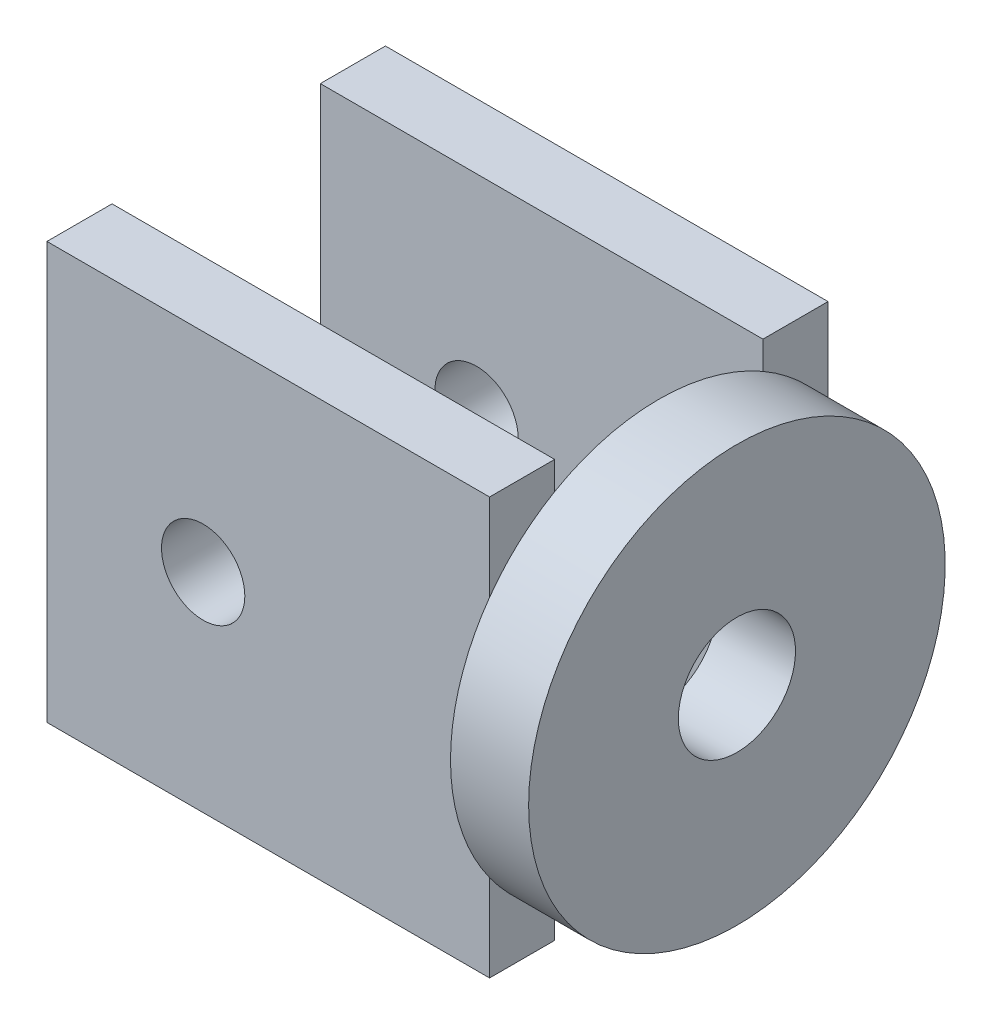
SolidWorks part; units mm, degrees
ref_plane "Front Plane" through (0, 0, 0) normal (0, 0, 1) x (1, 0, 0)
ref_plane "Top Plane" through (0, 0, 0) normal (0, 1, 0) x (1, 0, 0)
ref_plane "Right Plane" through (0, 0, 0) normal (1, 0, 0) x (0, 0, -1)
sketch "Base Sketch" plane through (0, 0, 0) normal (0, 0, 1) x (1, 0, 0)
  line L0 (-3000, 0) -> (3000, 0) construction
  line L1 (-3, 0) -> (0, 0)
  line L2 (0, 0) -> (0, 8)
  line L3 (0, 8) -> (-3, 8)
  line L4 (-3, 8) -> (-3, 0)
revolve "Base" add sketch "Base Sketch" angle 360 about L0
ref_axis "Engine Axis" through (1, 0, 0) along (-1, 0, 0)
sketch "Cheek Block Sketch" plane through (0, 0, 0) normal (0, 0, 1) x (1, 0, 0)
  line L0 (-20, -8) -> (-3, -8)
  line L1 (-3, -8) -> (-3, 8)
  line L2 (-3, 8) -> (-20, 8)
  line L3 (-20, 8) -> (-20, -8)
extrude "Cheek Block" add sketch "Cheek Block Sketch" along normal mid plane 13
sketch "Gap Sketch" plane through (0, 0, 0) normal (0, 0, 1) x (1, 0, 0)
  line L0 (-21, -9) -> (-3, -9)
  line L1 (-3, -9) -> (-3, 9)
  line L2 (-3, 9) -> (-21, 9)
  line L3 (-21, 9) -> (-21, -9)
extrude "Gap" cut sketch "Gap Sketch" against normal mid plane 8
sketch "Pin Hole Sketch" plane through (0, 0, 0) normal (0, 0, 1) x (1, 0, 0)
  circle A0 centre (-14, 0) radius 1.6
extrude "Pin Hole" cut sketch "Pin Hole Sketch" against normal mid plane 17
sketch "Screw Hole Sketch" plane through (0, 0, 0) normal (0, 0, 1) x (1, 0, 0)
  line L0 (-3000, 0) -> (3000, 0) construction
  line L1 (-3.5, 0) -> (0.5, 0)
  line L2 (0.5, 0) -> (0.5, 2.25)
  line L3 (0.5, 2.25) -> (-3.5, 2.25)
  line L4 (-3.5, 2.25) -> (-3.5, 0)
revolve "Screw Hole" cut sketch "Screw Hole Sketch" angle 360 about L0
